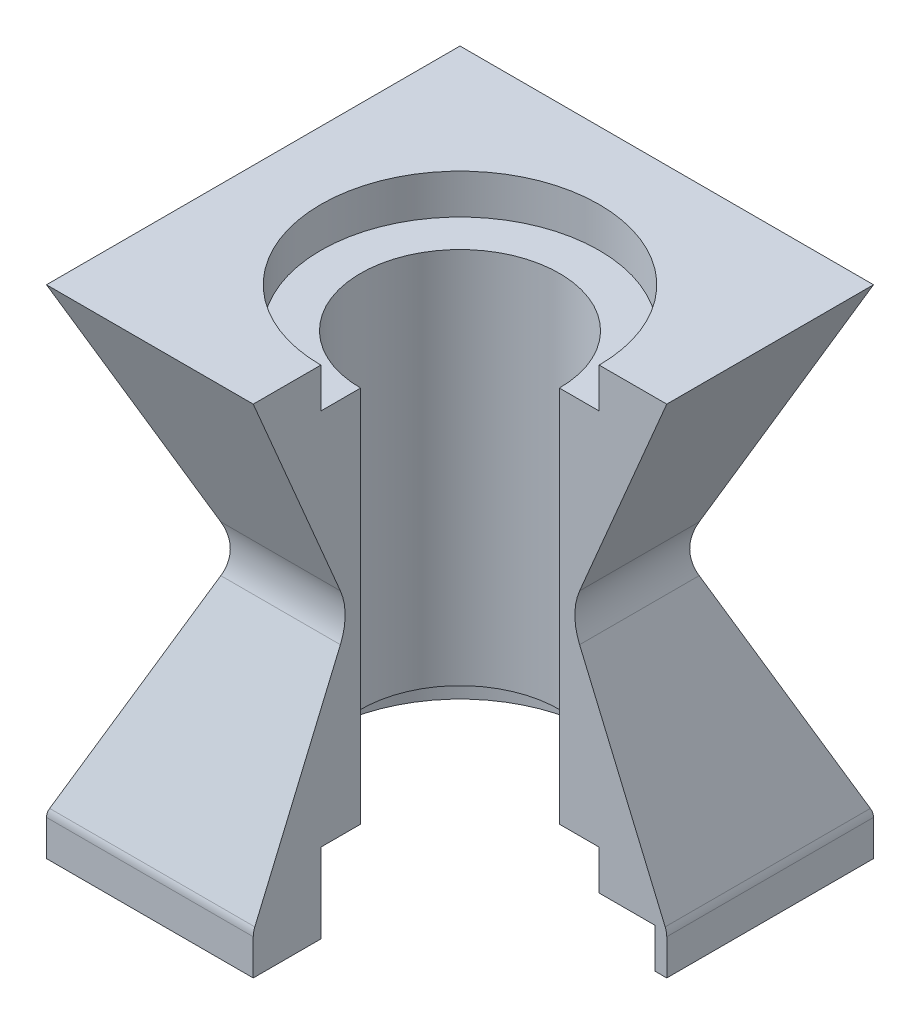
SolidWorks part; units mm, degrees
material "Cast Stainless Steel"
ref_plane "Front Plane" through (0, 0, 0) normal (0, 0, 1) x (1, 0, 0)
ref_plane "Top Plane" through (0, 0, 0) normal (0, 1, 0) x (1, 0, 0)
ref_plane "Right Plane" through (0, 0, 0) normal (1, 0, 0) x (0, 0, -1)
sketch "Sketch1" plane through (0, 0, 0) normal (0, 1, 0) x (1, 0, 0)
  line L1 (0, 0) -> (104, 0)
  line L2 (0, 0) -> (0, 104)
  line L3 (0, 104) -> (104, 104)
  line L4 (104, 0) -> (104, 104)
  dimension "D1" = 104
  dimension "D2" = 104
extrude "Boss-Extrude1" add sketch "Sketch1" along normal blind 57.5 draft 23
mirror "Mirror1" about plane through (0, 57.5, 0) normal (0, -1, 0) of bodies 101
sketch "Sketch2" plane through (0, 115, 0) normal (0, 1, 0) x (1, 0, 0)
  line L0 (104, 52) -> (0, 52) construction
  line L1 (104, 0) -> (104, 104) construction
  line L2 (0, 104) -> (0, 0) construction
  line L3 (52, 104) -> (52, 0) construction
  line L4 (104, 104) -> (0, 104) construction
  line L5 (0, 0) -> (104, 0) construction
  circle A0 centre (52, 52) radius 25
  dimension "D1" = 50
  dimension "D2" = 52
  dimension "D3" = 52
extrude "Cut-Extrude1" cut sketch "Sketch2" against normal through all contours A0
fillet "Fillet1" radius 15 4 edges at (79.5927, 57.5, -52) (52, 57.5, -79.5927) (24.4073, 57.5, -52) (52, 57.5, -24.4073)
sketch "Sketch3" plane through (0, 115, 0) normal (0, 1, 0) x (1, 0, 0)
  line L0 (0, 104) -> (0, 0) construction
  line L1 (0, 0) -> (104, 0) construction
  circle A0 centre (52, 52) radius 35
  point P2 (0, 0)
  point P4 (64.7039, 19.387)
  dimension "D1" = 70
  dimension "D2" = 52
  dimension "D3" = 52
extrude "Cut-Extrude2" cut sketch "Sketch3" against normal blind 10
sketch "Sketch4" plane through (0, 0, 0) normal (0, -1, 0) x (1, 0, 0)
  circle A0 centre (52, -52) radius 35
  dimension "D1" = 70
extrude "Cut-Extrude3" cut sketch "Sketch4" against normal blind 10
sketch "Sketch5" plane through (0, 115, 0) normal (0, 1, 0) x (1, 0, 0)
  line L0 (104, 52) -> (52, 52)
  line L5 (104, 0) -> (104, 104) construction
  line L6 (52, 52) -> (52, 0)
  line L7 (0, 0) -> (104, 0) construction
  line L8 (52, 0) -> (104, 0)
  line L9 (104, 0) -> (104, 52)
extrude "Cut-Extrude4" cut sketch "Sketch5" against normal through all contours L9 L0 L6 L8
sketch "Sketch7" plane through (0, 0, 0) normal (0, -1, 0) x (1, 0, 0)
  line L0 (49, -17) -> (49, -3)
  line L1 (49, -3) -> (3, -3)
  line L2 (3, -3) -> (3, -101)
  line L3 (3, -101) -> (101, -101)
  line L4 (101, -101) -> (101, -52)
  line L5 (101, -52) -> (104, -52)
  line L6 (52, -17) -> (52, 0)
  line L7 (52, 0) -> (0, 0)
  line L8 (0, 0) -> (52, 0) construction
  line L9 (0, 0) -> (0, -104)
  line L10 (0, -104) -> (104, -104)
  line L11 (104, -104) -> (104, -52)
  line L12 (49, -17) -> (52, -17)
  dimension "D1" = 3
extrude "Boss-Extrude2" add sketch "Sketch7" along normal blind 10
fillet "Fillet2" radius 5 4 edges at (0, 0, -52) (26, 0, 0) (104, 0, -78) (52, 0, -101)
fillet "Fillet3" radius 5 1 edges at (52, 0, -104)
sketch "Sketch8" plane through (0, 0, 0) normal (0, -1, 0) x (1, 0, 0)
  line L0 (0, 0) -> (67.8141, -67.373) construction
  line L1 (52, 0) -> (52, -52) construction
  line L2 (110.909, -52) -> (-22.4081, -52) construction
  line L3 (12.5684, -12.4867) -> (23.2096, -23.0587) construction
  line L4 (14.6828, -10.3585) -> (25.324, -20.9304)
  line L5 (10.4541, -14.6149) -> (21.0952, -25.1869)
  line L6 (12.5684, -91.5133) -> (23.2096, -80.9413) construction
  line L7 (14.6828, -93.6415) -> (25.324, -83.0696)
  line L8 (10.4541, -89.3851) -> (21.0952, -78.8131)
  line L9 (101.4584, -1.8486) -> (35.5559, -68.5071) construction
  line L10 (91.8349, -90.8541) -> (81.1422, -80.3342) construction
  line L11 (93.9388, -88.7155) -> (83.2462, -78.1957)
  line L12 (89.7309, -92.9926) -> (79.0382, -82.4727)
  circle A0 centre (52, -52) radius 50 construction
  arc A1 (14.6828, -10.3585) -> (10.4541, -14.6149) centre (12.5684, -12.4867) ccw
  arc A2 (21.0952, -25.1869) -> (25.324, -20.9304) centre (23.2096, -23.0587) ccw
  arc A3 (14.6828, -93.6415) -> (10.4541, -89.3851) centre (12.5684, -91.5133) cw
  arc A4 (21.0952, -78.8131) -> (25.324, -83.0696) centre (23.2096, -80.9413) cw
  arc A5 (93.9388, -88.7155) -> (89.7309, -92.9926) centre (91.8349, -90.8541) cw
  arc A6 (79.0382, -82.4727) -> (83.2462, -78.1957) centre (81.1422, -80.3342) cw
  point P13 (17.889, -17.7727)
  point P20 (17.889, -86.2273)
  point P27 (35.5559, -68.5071)
  point P30 (86.4885, -85.5941)
  dimension "D1" = 100
  dimension "D3" = 3
  dimension "D2" = 15
extrude "Cut-Extrude5" cut sketch "Sketch8" against normal blind 10
equation "\"a\"= 115mm"
equation "\"b\"= 104mm"
equation "\"c\"= 23deg"
equation "\"D1@Sketch1\"=\"b\""
equation "\"D2@Sketch1\"=\"b\""
equation "\"D2@Sketch3\"=\"b\"/2"
